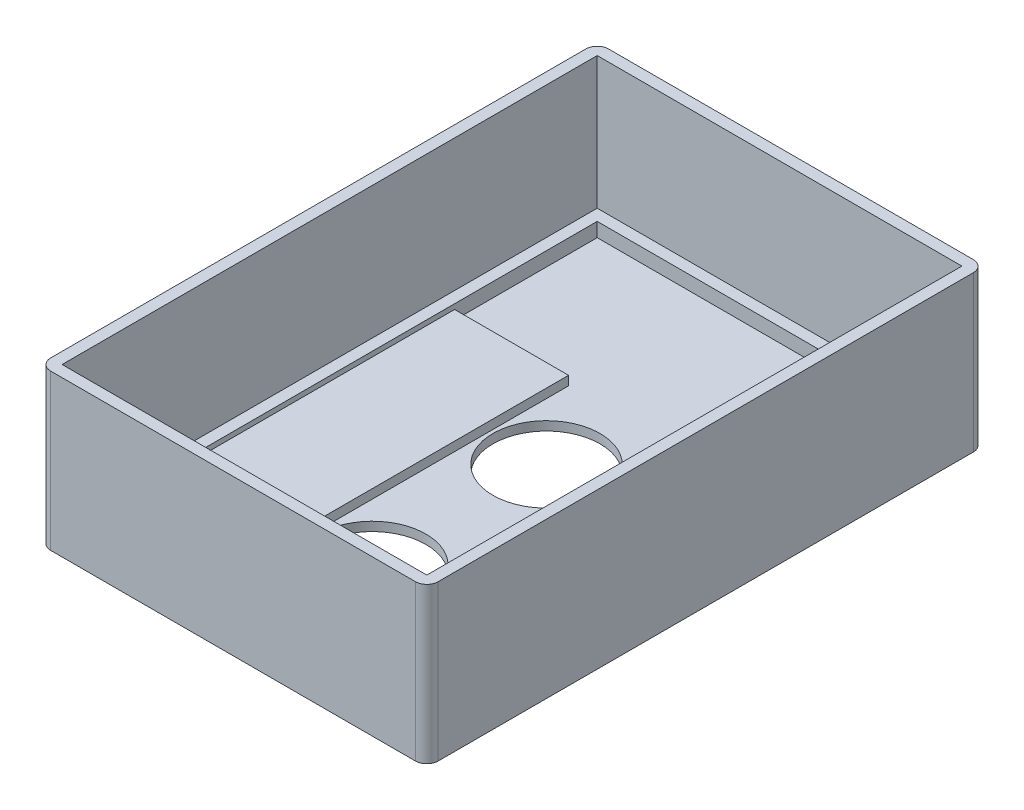
SolidWorks part; units mm, degrees
material "ABS"
ref_plane "Front Plane" through (0, 0, 0) normal (0, 0, 1) x (1, 0, 0)
ref_plane "Top Plane" through (0, 0, 0) normal (0, 1, 0) x (1, 0, 0)
ref_plane "Right Plane" through (0, 0, 0) normal (1, 0, 0) x (0, 0, -1)
sketch "Sketch1" plane through (0, 0, 0) normal (0, 1, 0) x (1, 0, 0)
  line L1 (86.36, 124.333) -> (0, 124.333)
  line L2 (86.36, 124.333) -> (86.36, 0)
  line L3 (86.36, 0) -> (0, 0)
  line L4 (0, 124.333) -> (0, 0)
extrude "Boss-Extrude1" add sketch "Sketch1" along normal blind 34.6202
sketch "Sketch3" plane through (0, 34.6202, 0) normal (0, 1, 0) x (1, 0, 0)
  line L1 (81.28, 119.253) -> (5.08, 119.253)
  line L2 (81.28, 119.253) -> (81.28, 5.08)
  line L3 (81.28, 5.08) -> (5.08, 5.08)
  line L4 (5.08, 119.253) -> (5.08, 5.08)
  line L5 (81.28, 119.253) -> (5.08, 5.08) construction
  line L6 (81.28, 5.08) -> (5.08, 119.253) construction
  point P0 (43.18, 62.1665)
extrude "Cut-Extrude1" cut sketch "Sketch3" against normal blind 30.5816
sketch "Sketch4" plane through (0, 34.6202, 0) normal (0, 1, 0) x (1, 0, 0)
  line L1 (83.82, 121.793) -> (2.54, 121.793)
  line L2 (83.82, 121.793) -> (83.82, 2.54)
  line L3 (83.82, 2.54) -> (2.54, 2.54)
  line L4 (2.54, 121.793) -> (2.54, 2.54)
  line L5 (83.82, 121.793) -> (2.54, 2.54) construction
  line L6 (83.82, 2.54) -> (2.54, 121.793) construction
  point P0 (43.18, 62.1665)
extrude "Cut-Extrude2" cut sketch "Sketch4" against normal blind 29.464
sketch "Sketch6" plane through (0, 4.0386, 0) normal (0, 1, 0) x (1, 0, 0)
  line L0 (81.28, 5.08) -> (81.28, 119.253) construction
  line L1 (5.08, 119.253) -> (81.28, 119.253)
  line L2 (5.08, 119.253) -> (5.08, 87.472)
  line L3 (30.48, 87.472) -> (5.08, 87.472)
  line L4 (81.28, 119.253) -> (81.28, 87.472)
  line L5 (5.08, 5.08) -> (81.28, 5.08) construction
  line L6 (55.88, 87.472) -> (81.28, 87.472)
  line L7 (30.48, 87.472) -> (30.48, 5.08)
  line L8 (30.48, 5.08) -> (55.88, 5.08)
  line L9 (55.88, 87.472) -> (55.88, 5.08)
extrude "Cut-Extrude3" cut sketch "Sketch6" against normal blind 2.032
sketch "Sketch8" plane through (0, 2.0066, 0) normal (0, 1, 0) x (1, 0, 0)
  circle A0 centre (43.18, 31.0388) radius 11.938
  circle A1 centre (43.18, 69.85) radius 11.938
extrude "Cut-Extrude4" cut sketch "Sketch8" against normal blind 2.032
fillet "Fillet1" radius 2.54 4 edges at (86.36, 17.3101, 0) (0, 17.3101, 0) (0, 17.3101, -124.333) (86.36, 17.3101, -124.333)
